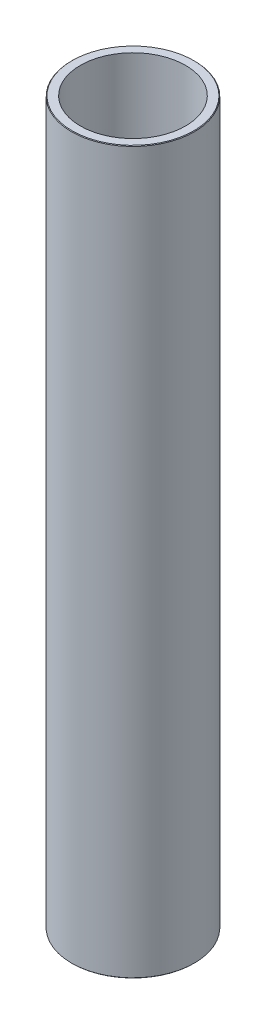
SolidWorks part; units mm, degrees
ref_plane "Front Plane" through (0, 0, 0) normal (0, 0, 1) x (1, 0, 0)
ref_plane "Top Plane" through (0, 0, 0) normal (0, 1, 0) x (1, 0, 0)
ref_plane "Right Plane" through (0, 0, 0) normal (1, 0, 0) x (0, 0, -1)
sketch "Sketch1" plane through (0, 0, 0) normal (0, 1, 0) x (1, 0, 0)
  circle A0 centre (0, 0) radius 50
  dimension "SHAFT_OD" = 100
extrude "Boss-Extrude1" add sketch "Sketch1" along normal blind 587.0456
sketch "Sketch2" plane through (0, 0, 0) normal (0, 1, 0) x (1, 0, 0)
  circle A0 centre (0, 0) radius 42.811
  dimension "BORE_D" = 85.6221
extrude "Cut-Extrude1" cut sketch "Sketch2" along normal through all
chamfer "Chamfer1" distance 0.4787 angle 45 2 edges at (0, 587.0456, 50) (0, 0, 50)
